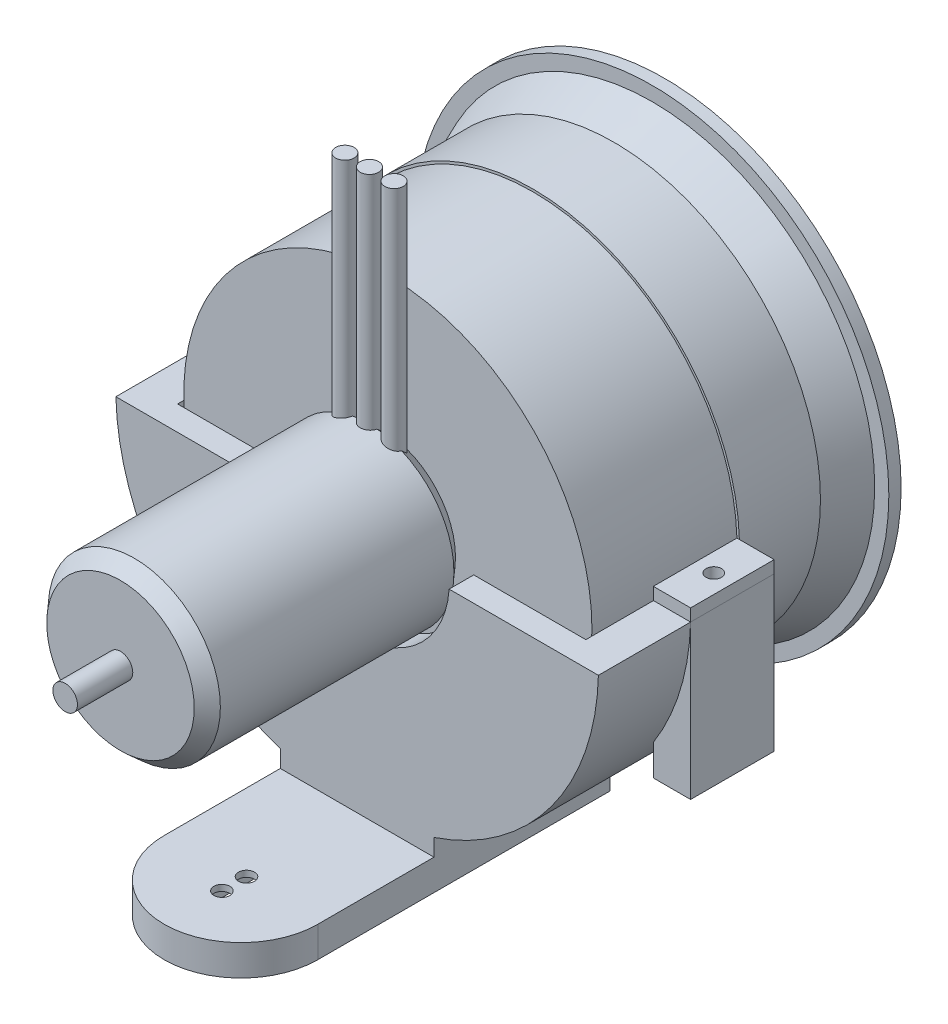
SolidWorks part; units mm, degrees
ref_plane "Front Plane" through (0, 0, 0) normal (1, 0, 0) x (0, 1, 0)
ref_plane "Top Plane" through (0, 0, 0) normal (0, 0, 1) x (0, 1, 0)
ref_plane "Right Plane" through (0, 0, 0) normal (0, 1, 0) x (-1, 0, 0)
sketch "Sketch1" plane through (0, 0, 0) normal (1, 0, 0) x (0, 1, 0)
  line L0 (0, 0) -> (0, -32.442) construction
  line L1 (0, 0) -> (38.5, 0)
  line L2 (38.5, 0) -> (38.5, 2)
  line L3 (38.5, 2) -> (36.2, 2)
  line L4 (36.2, 2) -> (33.6, 8.225)
  line L5 (33.6, 8.225) -> (33.6, 21.4)
  line L6 (33.2, 21.4) -> (33.2, 45)
  line L7 (33.2, 45) -> (5, 45)
  line L9 (5, 46) -> (12, 46)
  line L10 (12, 46) -> (14, 48.25)
  line L11 (14, 48.25) -> (14, 86.25)
  line L12 (14, 86.25) -> (12, 88.5)
  line L13 (12, 88.5) -> (2, 88.5)
  line L14 (2, 88.5) -> (2, 97.5)
  line L15 (2, 97.5) -> (0, 97.5)
  line L17 (33.2, 21.4) -> (33.6, 21.4)
  line L19 (0, 97.5) -> (0, 0)
  line L20 (5, 46) -> (5, 45)
  dimension "D1" = 77
  dimension "D2" = 72.4
  dimension "D3" = 67.2
  dimension "D4" = 66.4
  dimension "D5" = 45
  dimension "D6" = 23.6
  dimension "D7" = 97.5
  dimension "D8" = 2
  dimension "D9" = 4
  dimension "D10" = 28
  dimension "D11" = 1
  dimension "D12" = 42.5
  dimension "D13" = 10
  dimension "D14" = 10
  dimension "D15" = 38
revolve "Revolve1" add sketch "Sketch1" angle 360 about L0
sketch "Sketch3" plane through (0, 0, 0) normal (1, 0, 0) x (0, 1, 0)
  line L0 (33.2, 45) -> (-33.2, 45) construction
  line L1 (-1, 35) -> (1, 35)
  line L2 (-1, 35) -> (-1, 21.4)
  line L3 (-1, 21.4) -> (1, 21.4)
  line L4 (1, 35) -> (1, 21.4)
  point P4 (0, 21.4)
  dimension "D1" = 13.6
  dimension "D2" = 10
  dimension "D3" = 2
extrude "Boss-Extrude1" add sketch "Sketch3" along normal mid plane 78.5
sketch "Sketch4" plane through (0, 1, 0) normal (0, 1, 0) x (-1, 0, 0)
  line L0 (-39.25, 35) -> (-33.1849, 35) construction
  line L1 (-39.25, 28.2) -> (-33.1849, 28.2) construction
  line L4 (-39.25, 21.4) -> (-39.25, 35) construction
  line L5 (-33.1849, 21.4) -> (-33.1849, 35) construction
  circle A0 centre (-36.2175, 28.2) radius 1.25
  dimension "D2" = 2.5
  dimension "D1" = 6.8
extrude "Cut-Extrude1" cut sketch "Sketch4" against normal through all
mirror "Mirror1" about plane through (0, 0, 0) normal (1, 0, 0) of "Cut-Extrude1"
sketch "Sketch5" plane through (0, 0, 0) normal (0, 1, 0) x (-1, 0, 0)
  line L2 (-12, 46) -> (12, 46) construction
  circle A0 centre (0, 48) radius 1.5
  circle A1 centre (4, 48) radius 1.5
  circle A2 centre (-4, 48) radius 1.5
  dimension "D1" = 3
  dimension "D2" = 0.5
  dimension "D3" = 1
  dimension "D4" = 1
extrude "Boss-Extrude5" add sketch "Sketch5" along normal blind 50
sketch "Sketch6" plane through (0, 0, 45) normal (0, 0, 1) x (1, 0, 0)
  line L0 (39.25, -1) -> (33.1849, -1)
  line L1 (-39.25, -1) -> (-33.2049, -1)
  line L2 (-39.25, -1) -> (-39.25, -26)
  line L3 (-39.25, -26) -> (-33.2049, -26)
  line L4 (-33.2049, -26) -> (-33.2049, -20.9522)
  line L5 (39.25, -1) -> (39.25, -26)
  line L6 (39.25, -26) -> (33.1849, -26)
  line L7 (33.1849, -26) -> (33.1849, -20.9839)
  arc A0 (-33.2049, -1) -> (33.2049, -1) centre (0, 0) ccw
  arc A1 (-39.25, -1) -> (39.25, -1) centre (0, 0) ccw
  circle A2 centre (0, 0) radius 33.2 construction
  dimension "D1" = 0.02
  dimension "D2" = 25
extrude "Boss-Extrude6" add sketch "Sketch6" against normal up to surface (23.6 mm away) and the other way blind 5 separate body contours L1 A1 L0 A0 region at (36.7349, -11.149, 45) up to face at (-36.4213, 0, 21.4)
extrude "Boss-Extrude7" add sketch "Sketch6<4>" along normal up to surface (-10 mm away) from surface contours A1 L7 L6 L5 | A1 L2 L3 L4 region at (36.9268, -19.1147, 45) region at (-36.932, -19.1085, 45) up to face at (36.2212, 0, 35) starting at face at (36.4213, 0, 21.4)
sketch "Sketch6<4>" plane through (0, 0, 45) normal (0, 0, 1) x (1, 0, 0) same geometry as "Sketch6"
sketch "Sketch7" plane through (0, -26, 0) normal (0, -1, 0) x (1, 0, 0)
  circle A0 centre (-36.2175, 28.2) radius 1.25 construction
  circle A1 centre (-36.2175, 28.2) radius 1.25
extrude "Cut-Extrude2" cut sketch "Sketch7" against normal through all
mirror "Mirror2" about plane through (0, 0, 0) normal (1, 0, 0) of "Cut-Extrude2"
sketch "Sketch8" plane through (0, 0, 50) normal (0, 0, 1) x (1, 0, 0)
  line L0 (-33.2049, -1) -> (-14.9666, -1)
  line L1 (33.2049, -1) -> (14.9666, -1)
  circle A0 centre (0, 0) radius 14 construction
  circle A1 centre (0, 0) radius 14 construction
  arc A2 (-14.9666, -1) -> (14.9666, -1) centre (0, 0) ccw
  circle A3 centre (0, 0) radius 15 construction
  arc A4 (-33.2049, -1) -> (33.2049, -1) centre (0, 0) ccw construction
  arc A5 (-33.2049, -1) -> (33.2049, -1) centre (0, 0) ccw
  dimension "D1" = 1
extrude "Boss-Extrude8" add sketch "Sketch8" against normal offset from surface (4 mm away) 1 up to face at (5, 0, 45)
ref_plane "Plane1" through (0, -45, 0) normal (0, -1, 0) x (1, 0, 0)
sketch "Sketch9" plane through (0, -45, 0) normal (0, -1, 0) x (1, 0, 0)
  line L0 (-33.2049, 21.4) -> (33.1849, 21.4) construction
  line L1 (-12.5, 81.4) -> (12.5, 81.4)
  line L2 (-12.5, 81.4) -> (-12.5, 21.4)
  line L3 (-12.5, 21.4) -> (12.5, 21.4)
  line L4 (12.5, 81.4) -> (12.5, 21.4)
  line L5 (4, 61.4257) -> (4, 72) construction
  line L6 (-4, 72) -> (-4, 61.4257) construction
  line L7 (4, 61.4257) -> (4, 72) construction
  line L8 (-4, 72) -> (-4, 61.4257) construction
  line L9 (4.05, 61.4257) -> (4.05, 72)
  line L10 (-4.05, 72) -> (-4.05, 61.4257)
  arc A0 (0, 38.025) -> (0, 57.975) centre (0, 48) ccw construction
  arc A1 (4, 61.4257) -> (5.15, 54.7416) centre (24, 61.4257) ccw construction
  arc A2 (4, 72) -> (-4, 72) centre (0, 72) ccw construction
  arc A3 (-5.15, 54.7416) -> (-4, 61.4257) centre (-24, 61.4257) ccw construction
  arc A4 (0, 57.975) -> (0, 38.025) centre (0, 48) ccw construction
  arc A5 (0, 38.025) -> (4.5207, 56.8918) centre (0, 48) ccw construction
  arc A6 (4, 61.4257) -> (4.5207, 56.8918) centre (24, 61.4257) ccw construction
  arc A7 (4, 72) -> (-4, 72) centre (0, 72) ccw construction
  arc A8 (-4.5207, 56.8918) -> (-4, 61.4257) centre (-24, 61.4257) ccw construction
  arc A9 (-4.5207, 56.8918) -> (0, 38.025) centre (0, 48) ccw construction
  arc A10 (4.05, 72) -> (-4.05, 72) centre (0, 72) ccw
  arc A11 (-4.5641, 56.9258) -> (-4.05, 61.4257) centre (-24, 61.4257) ccw
  arc A12 (-4.5641, 56.9258) -> (0, 37.975) centre (0, 48) ccw
  arc A13 (0, 37.975) -> (4.5641, 56.9258) centre (0, 48) ccw
  arc A14 (4.05, 61.4257) -> (4.5641, 56.9258) centre (24, 61.4257) ccw
  point P6 (0, 21.4)
  dimension "D1" = 60
  dimension "D2" = 25
  dimension "D3" = 0.05
extrude "Boss-Extrude9" add sketch "Sketch9" against normal blind 5 separate body contours A14 L9 A10 L10 A11 A12 A13 | L4 L1 L2 L3 L9 A14 A13 A12 A11 L10 A10 region at (0, -45, 80.75) region at (0, -45, 53.7265)
extrude "Cut-Extrude3" cut sketch "Sketch9<3>" against normal blind 4 contours A14 L9 A10 L10 A11 A12 A13 region at (0, -45, 53.7265)
sketch "Sketch9<3>" plane through (0, -45, 0) normal (0, -1, 0) x (1, 0, 0) same geometry as "Sketch9"
sketch "Sketch10" plane through (0, -40, 0) normal (0, 1, 0) x (-1, 0, 0)
  line L0 (39.25, 50) -> (-39.25, 50) construction
  line L1 (-12.5, 50) -> (12.5, 50)
  line L2 (-12.5, 50) -> (-12.5, 21.4)
  line L3 (-12.5, 21.4) -> (12.5, 21.4)
  line L4 (12.5, 50) -> (12.5, 21.4)
  line L5 (-33.1849, 21.4) -> (33.2049, 21.4) construction
  line L6 (12.5, 81.4) -> (12.5, 21.4) construction
  line L7 (-12.5, 81.4) -> (-12.5, 21.4) construction
extrude "Boss-Extrude10" add sketch "Sketch10" along normal up to surface (2.7802 mm away) up to face at (-0.0055, -18.1561, 35.35)
sketch "Sketch11" plane through (0, -40, 0) normal (0, 1, 0) x (1, 0, 0)
  arc A0 (0, -69.3) -> (0, -66.7) centre (0, -68) ccw construction
  arc A1 (0, -66.7) -> (0, -69.3) centre (0, -68) ccw construction
  arc A2 (0, -73.3) -> (0, -70.7) centre (0, -72) ccw construction
  arc A3 (0, -70.7) -> (0, -73.3) centre (0, -72) ccw construction
  arc A4 (0, -69.3) -> (0, -66.7) centre (0, -68) ccw
  arc A5 (0, -66.7) -> (0, -69.3) centre (0, -68) ccw
  arc A6 (0, -73.3) -> (0, -70.7) centre (0, -72) ccw
  arc A7 (0, -70.7) -> (0, -73.3) centre (0, -72) ccw
extrude "Cut-Extrude4" cut sketch "Sketch11" against normal through all
fillet "Fillet1" 2 edges at (-12.5, -42.5, 81.4) (12.5, -42.5, 81.4) type full round first side face at (-12.5, -40.7399, 50.9333) second side face at (12.5, -40.7399, 50.9333) middle face at (0, -42.5, 81.4)
delete or keep bodies "Body-Delete/Keep 1" [suppressed] type delete bodies bodies 105
